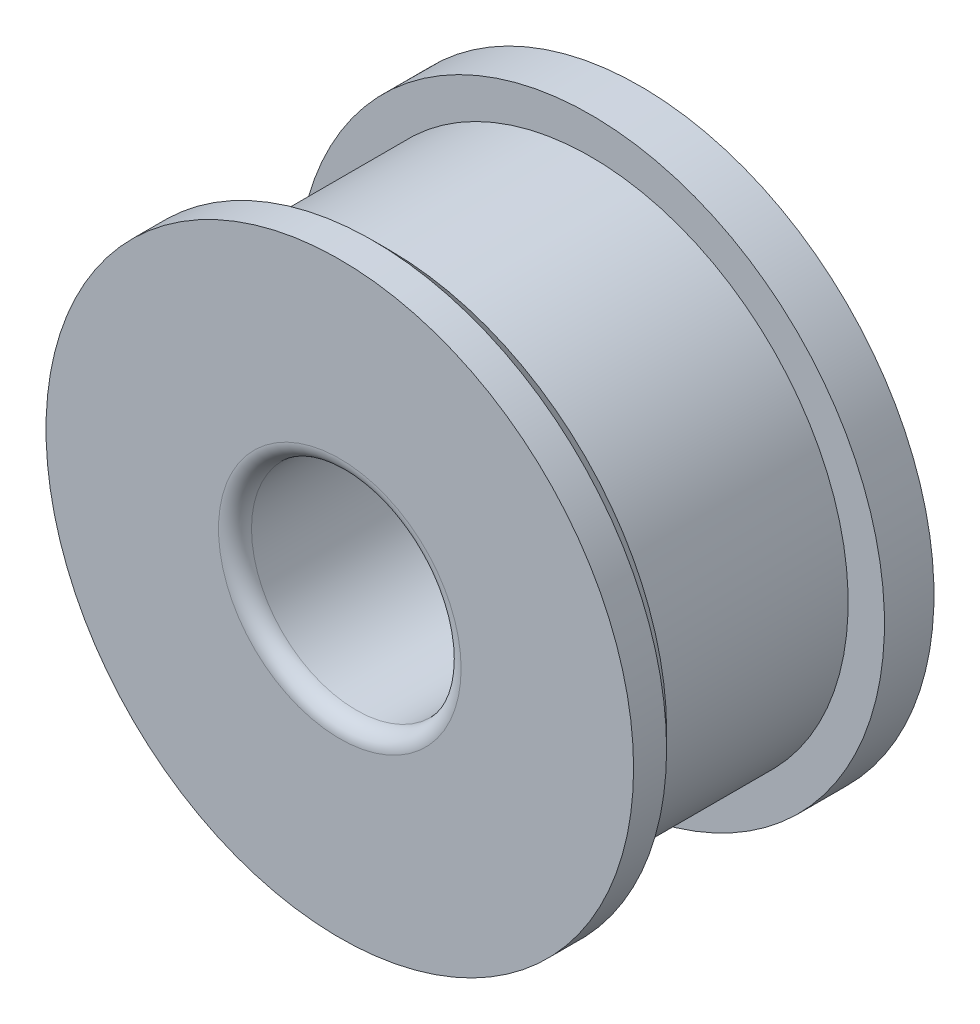
SolidWorks part; units mm, degrees
ref_plane "Plano frontal" through (0, 0, 0) normal (0, 0, 1) x (1, 0, 0)
ref_plane "Plano superior" through (0, 0, 0) normal (0, 1, 0) x (1, 0, 0)
ref_plane "Plano direito" through (0, 0, 0) normal (1, 0, 0) x (0, 0, -1)
sketch "Esboço1" plane through (0, 0, 0) normal (0, 0, 1) x (1, 0, 0)
  line L1 (48.7, 0.625) -> (-48.7, 0.625)
  line L2 (48.7, 0.625) -> (48.7, -0.625)
  line L3 (48.7, -0.625) -> (-48.7, -0.625)
  line L4 (-48.7, 0.625) -> (-48.7, -0.625)
  line L5 (48.7, 0.625) -> (-48.7, -0.625) construction
  line L6 (48.7, -0.625) -> (-48.7, 0.625) construction
  point P0 (0, 0)
  dimension "D1" = 97.4
  dimension "D2" = 1.25
extrude "Ressalto-extrusão1" add sketch "Esboço1" along normal blind 6.2
sketch "Esboço2" plane through (0, -0.625, 0) normal (0, 1, 0) x (1, 0, 0)
  line L0 (48.7, -6.2) -> (48.7, 0) construction
  line L1 (-48.7, 0) -> (48.7, 0)
  line L2 (-48.7, 0) -> (-48.7, -1.25)
  line L3 (-48.7, -1.25) -> (48.7, -1.25)
  line L4 (48.7, 0) -> (48.7, -1.25)
  dimension "D1" = 1.25
extrude "Ressalto-extrusão2" add sketch "Esboço2" along normal blind 40.6 contours L3 L4 L1 L2
fillet "Filete1" radius 1 4 edges at (48.7, 39.975, 0.625) (-48.7, 39.975, 0.625) (48.7, 0, 6.2) (-48.7, 0, 6.2)
sketch "Esboço3" plane through (0, 0, 1.25) normal (0, 0, 1) x (1, 0, 0)
  line L0 (27.7, 34.975) -> (30.7, 34.975) construction
  line L11 (39.7, 33.975) -> (43.7, 33.975)
  line L12 (39.7, 33.975) -> (39.7, 27.975)
  line L13 (39.7, 27.975) -> (43.7, 27.975)
  line L14 (43.7, 33.975) -> (43.7, 27.975)
  line L15 (39.7, 11.975) -> (43.7, 11.975)
  line L16 (39.7, 11.975) -> (39.7, 5.975)
  line L17 (39.7, 5.975) -> (43.7, 5.975)
  line L18 (43.7, 11.975) -> (43.7, 5.975)
  line L19 (-36.7, 12.975) -> (-30.7, 12.975)
  line L20 (-36.7, 12.975) -> (-36.7, 4.975)
  line L21 (-36.7, 4.975) -> (-30.7, 4.975)
  line L22 (-30.7, 12.975) -> (-30.7, 4.975)
  line L23 (27.7, 36.975) -> (30.7, 36.975)
  line L24 (27.7, 32.975) -> (30.7, 32.975)
  line L25 (0, 39.975) -> (0, 2.975) construction
  line L26 (-47.7, 39.975) -> (47.7, 39.975) construction
  line L27 (-47.7, 39.975) -> (47.7, 39.975) construction
  line L28 (-48.7, 38.975) -> (-48.7, 0.625) construction
  line L29 (-36.7, 34.975) -> (-30.7, 34.975)
  line L30 (-36.7, 34.975) -> (-36.7, 26.975)
  line L31 (-36.7, 26.975) -> (-30.7, 26.975)
  line L32 (-30.7, 34.975) -> (-30.7, 26.975)
  line L33 (48.7, 38.975) -> (48.7, 0.625) construction
  line L34 (48.7, 19.8) -> (0, 19.8) construction
  circle A5 centre (-43.7, 4.975) radius 2
  circle A6 centre (0, 4.975) radius 2
  circle A7 centre (38.95, 19.8) radius 2.5
  circle A8 centre (14.7, 19.8) radius 6
  arc A9 (27.7, 36.975) -> (27.7, 32.975) centre (27.7, 34.975) ccw
  arc A10 (30.7, 32.975) -> (30.7, 36.975) centre (30.7, 34.975) ccw
  point P22 (29.2, 34.975)
  point P33 (25.7, 34.975)
  point P34 (32.7, 34.975)
  dimension "D14" = 5
  dimension "D16" = 16
  dimension "D27" = 4
  dimension "D3" = 4
  dimension "D6" = 12
  dimension "D17" = 5
  dimension "D4" = 35
  dimension "D8" = 34
  dimension "D9" = 6
  dimension "D10" = 4
  dimension "D11" = 6
  dimension "D12" = 4
  dimension "D13" = 5
  dimension "D15" = 6
  dimension "D18" = 9.75
  dimension "D19" = 8
  dimension "D20" = 6
  dimension "D21" = 8
  dimension "D22" = 6
  dimension "D23" = 12
  dimension "D24" = 12
  dimension "D25" = 5
  dimension "D26" = 14
  dimension "D28" = 5
  dimension "D29" = 35
  dimension "D30" = 0
  dimension "D31" = 4
  dimension "D32" = 7
  dimension "D33" = 3
  dimension "D34" = 16
extrude "Corte-extrusão1" cut sketch "Esboço3" against normal blind 40.6
sketch "Esboço5" plane through (0, 0, 0) normal (0, 0, -1) x (-1, 0, 0)
  line L0 (-20.7, 19.8) -> (48.7, 19.8) construction
  line L1 (48.7, 38.975) -> (48.7, -0.625) construction
  line L2 (47.7, 39.975) -> (-47.7, 39.975) construction
  line L3 (48.7, 23.975) -> (48.7, 19.8) construction
  circle A0 centre (4.1, 23.975) radius 2
  circle A1 centre (25.7, 19.8) radius 3
  circle A2 centre (-14.7, 19.8) radius 6 construction
  dimension "D1" = 23
  dimension "6" = 6
  dimension "D2" = 4
  dimension "D3" = 16
  dimension "D4" = 44.6
sketch "Esboço6" plane through (0, 0, 0) normal (0, 0, -1) x (-1, 0, 0)
  circle A0 centre (25.7, 19.8) radius 3
  dimension "D1" = 6
extrude "Ressalto-extrusão3" add sketch "Esboço6" against normal blind 22.5
sketch "Esboço7" plane through (0, 0, 0) normal (0, 0, -1) x (-1, 0, 0)
  circle A0 centre (4.1, 23.975) radius 2.25
  dimension "D1" = 4.5
extrude "Ressalto-extrusão4" add sketch "Esboço7" against normal blind 12.3
fillet "Filete2" radius 0.25 2 edges at (-6.35, 23.975, 12.3) (-28.7, 19.8, 22.5)
sketch "Esboço12" plane through (0, 0, 0) normal (0, 0, 1) x (1, 0, 0)
  circle A0 centre (-4.1, 23.975) radius 4
  dimension "D1" = 8
extrude "Ressalto-extrusão7" add sketch "Esboço12" along normal blind 3
sketch "Esboço13" plane through (0, 0, 0) normal (0, 0, -1) x (-1, 0, 0)
  circle A0 centre (25.7, 19.8) radius 4.5
  dimension "D1" = 9
extrude "Ressalto-extrusão8" add sketch "Esboço13" against normal blind 8.1
sketch "Esboço8" plane through (0, 0, 3) normal (0, 0, 1) x (1, 0, 0)
  circle A0 centre (-4.1, 23.975) radius 16.365
  circle A1 centre (-4.1, 23.975) radius 2.3
  dimension "D1" = 32.73
  dimension "D2" = 4.6
extrude "Ressalto-extrusão5" add sketch "Esboço8" along normal blind 4
sketch "Esboço9" plane through (0, 0, 3) normal (0, 0, 1) x (1, 0, 0)
  circle A1 centre (-4.1, 23.975) radius 4
  circle A2 centre (-4.1, 23.975) radius 2.3
  dimension "D1" = 8
extrude "Ressalto-extrusão6" add sketch "Esboço9" along normal blind 8.9
sketch "Esboço10" plane through (0, 0, 7) normal (0, 0, 1) x (1, 0, 0)
  circle A0 centre (-4.1, 23.975) radius 4.9
  circle A1 centre (-4.1, 23.975) radius 13.865
  circle A2 centre (-4.1, 23.975) radius 16.365 construction
  dimension "D1" = 9.8
  dimension "D2" = 2.5
extrude "Corte-extrusão2" cut sketch "Esboço10" against normal blind 1
sketch "Esboço11" plane through (0, 0, 3) normal (0, 0, -1) x (-1, 0, 0)
  circle A1 centre (4.1, 23.975) radius 13.86
  circle A2 centre (4.1, 23.975) radius 4.9
extrude "Corte-extrusão3" cut sketch "Esboço11" against normal blind 1
sketch "Esboço14" plane through (0, 0, 8.1) normal (0, 0, 1) x (1, 0, 0)
  circle A0 centre (-25.7, 19.8) radius 18.34
  circle A1 centre (-25.7, 19.8) radius 3.1
  circle A2 centre (-25.7, 19.8) radius 3 construction
  dimension "D1" = 36.68
  dimension "D2" = 0.1
extrude "Ressalto-extrusão9" add sketch "Esboço14" along normal blind 4
sketch "Esboço15" plane through (0, 0, 8.1) normal (0, 0, 1) x (1, 0, 0)
  circle A0 centre (-25.7, 19.8) radius 7.8
  circle A1 centre (-25.7, 19.8) radius 3.1
  dimension "D1" = 15.6
extrude "Ressalto-extrusão10" add sketch "Esboço15" along normal blind 11.6
sketch "Esboço16" plane through (0, 0, 19.7) normal (0, 0, 1) x (1, 0, 0)
  circle A0 centre (-25.7, 19.8) radius 3.1
  circle A1 centre (-25.7, 19.8) radius 8.9
  dimension "D1" = 17.8
extrude "Ressalto-extrusão11" add sketch "Esboço16" against normal blind 1.5
chamfer "Chanfro1" distance 0.5 angle 45 1 edges at (-16.8, 19.8, 18.2)
sketch "Esboço17" plane through (0, 0, 19.7) normal (0, 0, 1) x (1, 0, 0)
  circle A0 centre (-25.7, 19.8) radius 3.1
  circle A1 centre (-25.7, 19.8) radius 3.5
  dimension "D1" = 7
extrude "Ressalto-extrusão12" add sketch "Esboço17" along normal blind 0.5
sketch "Esboço18" plane through (0, 0, 12.1) normal (0, 0, 1) x (1, 0, 0)
  circle A0 centre (-25.7, 19.8) radius 15.84
  circle A1 centre (-25.7, 19.8) radius 8.9
  circle A2 centre (-25.7, 19.8) radius 18.34 construction
  dimension "D1" = 2.5
  dimension "D2" = 17.8
extrude "Corte-extrusão4" cut sketch "Esboço18" against normal blind 1
sketch "Esboço19" plane through (0, 0, 8.1) normal (0, 0, -1) x (-1, 0, 0)
  circle A0 centre (25.7, 19.8) radius 8.9
  circle A1 centre (25.7, 19.8) radius 15.825
extrude "Corte-extrusão5" cut sketch "Esboço19" against normal blind 1
sketch "Esboço20" plane through (0, 0, 20.2) normal (0, 0, 1) x (1, 0, 0)
  line L0 (-28.3227, 20.6269) -> (-29.675, 21.0533)
  line L3 (-23.7555, 21.7445) -> (-22.4747, 23.0253)
  line L4 (-25.2225, 22.5082) -> (-24.9763, 23.9046)
  line L5 (-23.7555, 17.8555) -> (-22.4747, 16.5747)
  line L6 (-25.2225, 17.0918) -> (-24.9763, 15.6954)
  line L7 (-28.3227, 18.9731) -> (-29.675, 18.5467)
  arc A0 (-22.6425, 24.5746) -> (-22.6425, 15.0254) centre (-25.7, 19.8) ccw
  arc A1 (-25.4411, 24.4906) -> (-29.9802, 21.7362) centre (-25.7, 19.8) ccw
  arc A2 (-28.3227, 20.6269) -> (-28.3227, 18.9731) centre (-25.7, 19.8) ccw
  arc A3 (-23.7555, 21.7445) -> (-25.2225, 22.5082) centre (-25.7, 19.8) ccw
  arc A4 (-25.2225, 17.0918) -> (-23.7555, 17.8555) centre (-25.7, 19.8) ccw
  arc A5 (-29.9802, 17.8638) -> (-25.4411, 15.1094) centre (-25.7, 19.8) ccw
  arc A6 (-22.4747, 16.5747) -> (-22.6425, 15.0254) centre (-23.1818, 15.8675) cw
  arc A7 (-22.4747, 23.0253) -> (-22.6425, 24.5746) centre (-23.1818, 23.7325) ccw
  arc A8 (-25.4411, 15.1094) -> (-24.9763, 15.6954) centre (-25.4687, 15.6086) ccw
  arc A9 (-25.4411, 24.4906) -> (-24.9763, 23.9046) centre (-25.4687, 23.9914) cw
  arc A10 (-29.9802, 17.8638) -> (-29.675, 18.5467) centre (-29.5246, 18.0698) cw
  arc A11 (-29.9802, 21.7362) -> (-29.675, 21.0533) centre (-29.5246, 21.5302) ccw
  dimension "D2" = 1
  dimension "D3" = 0.5
  dimension "D1" = 35
  dimension "D4" = 35
  dimension "D5" = 35
extrude "Ressalto-extrusão13" add sketch "Esboço20" along normal blind 0.5
sketch "Esboço21" plane through (0, 0, 0) normal (0, 0, -1) x (-1, 0, 0)
  line L0 (-29.3939, 34.975) -> (0, 4.975) construction
  line L1 (3.3061, 4.975) -> (-3.6939, 4.975) construction
  line L2 (3.5952, 5.1615) -> (2.7796, 20.8817)
  line L3 (-13.4337, 37.4293) -> (-29.134, 38.5656)
  line L4 (0, 1.375) -> (-4.8727, 1.375)
  line L5 (-32.9939, 34.975) -> (-32.9939, 30.076)
  line L6 (-32.9939, 30.076) -> (-30.4878, 27.5182)
  line L7 (-7.4776, 4.0335) -> (-4.8727, 1.375)
  circle A2 centre (0, 4.975) radius 1.75
  circle A3 centre (-29.3939, 34.975) radius 1.75
  arc A4 (-30.4878, 27.5182) -> (-7.4776, 4.0335) centre (-14.6969, 19.975) ccw
  arc A5 (0, 1.375) -> (3.5952, 5.1615) centre (0, 4.975) ccw
  arc A7 (-29.134, 38.5656) -> (-32.9939, 34.975) centre (-29.3939, 34.975) ccw
  arc A9 (2.7796, 20.8817) -> (-13.4337, 37.4293) centre (-14.6969, 19.975) ccw
  dimension "D2" = 3.5
  dimension "D3" = 3.5
  dimension "D4" = 35
  dimension "D5" = 7.2
  dimension "D1" = 42
  dimension "D7" = 6
extrude "Ressalto-extrusão14" add sketch "Esboço21" along normal blind 0.92
sketch "Esboço23" plane through (0, 0, 0) normal (0, 0, 1) x (1, 0, 0)
  circle A0 centre (14.7, 19.8) radius 17.675
extrude "Ressalto-extrusão15" add sketch "Esboço23" against normal blind 15
fillet "Filete4" radius 1 1 edges at (32.375, 19.8, -15)
sketch "Esboço24" plane through (0, 0, -0.92) normal (0, 0, -1) x (-1, 0, 0)
  circle A0 centre (0, 4.975) radius 1.75
  circle A1 centre (0, 4.975) radius 2.05
  circle A2 centre (-29.3939, 34.975) radius 1.75
  circle A3 centre (-29.3939, 34.975) radius 2.05
  dimension "D1" = 0.3
  dimension "D2" = 0.3
extrude "Ressalto-extrusão16" add sketch "Esboço24" along normal blind 1
sketch "Esboço25" plane through (0, 0, -15) normal (0, 0, -1) x (-1, 0, 0)
  circle A0 centre (-14.7, 19.8) radius 2.5
  dimension "D1" = 5
extrude "Ressalto-extrusão17" add sketch "Esboço25" along normal blind 0.1
sketch "Esboço26" plane through (0, 0, -15.1) normal (0, 0, -1) x (-1, 0, 0)
  circle A0 centre (-14.7, 19.8) radius 1
  dimension "D1" = 2
extrude "Ressalto-extrusão18" add sketch "Esboço26" along normal blind 0.5
fillet "Filete6" radius 0.1 1 edges at (12.2, 19.8, -15.1)
sketch "Esboço27" plane through (0, 0, -15) normal (0, 0, 1) x (1, 0, 0)
  circle A0 centre (14.7, 19.8) radius 4.99
  dimension "D1" = 9.98
extrude "Ressalto-extrusão19" add sketch "Esboço27" along normal blind 16.57
sketch "Esboço28" plane through (0, 0, -15.6) normal (0, 0, -1) x (-1, 0, 0)
  circle A0 centre (-14.7, 19.8) radius 1
extrude "Ressalto-extrusão20" add sketch "Esboço28" against normal blind 25
fillet "Filete5" radius 0.25 2 edges at (13.7, 19.8, -15.6) (13.7, 19.8, 9.4)
ref_plane "Plano2" through (0, 0, 9.15) normal (0, 0, 1) x (1, 0, 0)
sketch "Esboço29" plane through (0, 0, 9.15) normal (0, 0, 1) x (1, 0, 0)
  circle A0 centre (14.7, 19.8) radius 3.59
  dimension "D1" = 7.18
extrude "Ressalto-extrusão21" add sketch "Esboço29" against normal blind 6
sketch "Esboço30" plane through (0, 0, 1.25) normal (0, 0, 1) x (1, 0, 0)
  circle A0 centre (0, 4.975) radius 2.7
  circle A1 centre (29.3939, 34.975) radius 2.7
  dimension "D1" = 5.4
  dimension "D2" = 5.4
extrude "Ressalto-extrusão22" add sketch "Esboço30" along normal blind 2
fillet "Filete7" radius 1.4 2 edges at (2.7, 4.975, 3.25) (32.0939, 34.975, 3.25)
sketch "Esboço31" plane through (0, 0, 3.25) normal (0, 0, 1) x (1, 0, 0)
  line L1 (29.0939, 37.175) -> (29.6939, 37.175)
  line L2 (28.8939, 36.975) -> (28.8939, 35.975)
  line L3 (29.0939, 32.775) -> (29.6939, 32.775)
  line L4 (29.8939, 36.975) -> (29.8939, 35.975)
  line L7 (31.3939, 35.475) -> (30.3939, 35.475)
  line L8 (31.5939, 35.275) -> (31.5939, 34.675)
  line L9 (31.3939, 34.475) -> (30.3939, 34.475)
  line L10 (27.1939, 35.275) -> (27.1939, 34.675)
  line L15 (28.8939, 33.975) -> (28.8939, 32.975)
  line L17 (29.8939, 33.975) -> (29.8939, 32.975)
  line L18 (28.3939, 35.475) -> (27.3939, 35.475)
  line L19 (28.3939, 34.475) -> (27.3939, 34.475)
  line L42 (-0.1421, 7.325) -> (0.4579, 7.325)
  line L43 (-0.3421, 7.125) -> (-0.3421, 6.125)
  line L44 (-0.1421, 2.925) -> (0.4579, 2.925)
  line L45 (0.6579, 7.125) -> (0.6579, 6.125)
  line L46 (2.1579, 5.625) -> (1.1579, 5.625)
  line L47 (2.3579, 5.425) -> (2.3579, 4.825)
  line L48 (2.1579, 4.625) -> (1.1579, 4.625)
  line L49 (-2.0421, 5.425) -> (-2.0421, 4.825)
  line L50 (-0.3421, 4.125) -> (-0.3421, 3.125)
  line L51 (0.6579, 4.125) -> (0.6579, 3.125)
  line L52 (-0.8421, 5.625) -> (-1.8421, 5.625)
  line L53 (-0.8421, 4.625) -> (-1.8421, 4.625)
  arc A0 (29.8939, 33.975) -> (30.3939, 34.475) centre (30.3939, 33.975) cw
  arc A1 (28.8939, 33.975) -> (28.3939, 34.475) centre (28.3939, 33.975) ccw
  arc A2 (29.8939, 35.975) -> (30.3939, 35.475) centre (30.3939, 35.975) ccw
  arc A3 (28.8939, 35.975) -> (28.3939, 35.475) centre (28.3939, 35.975) cw
  arc A4 (28.8939, 32.975) -> (29.0939, 32.775) centre (29.0939, 32.975) ccw
  arc A5 (29.6939, 32.775) -> (29.8939, 32.975) centre (29.6939, 32.975) ccw
  arc A6 (31.5939, 34.675) -> (31.3939, 34.475) centre (31.3939, 34.675) cw
  arc A7 (31.3939, 35.475) -> (31.5939, 35.275) centre (31.3939, 35.275) cw
  arc A8 (29.6939, 37.175) -> (29.8939, 36.975) centre (29.6939, 36.975) cw
  arc A9 (29.0939, 37.175) -> (28.8939, 36.975) centre (29.0939, 36.975) ccw
  arc A10 (27.3939, 35.475) -> (27.1939, 35.275) centre (27.3939, 35.275) ccw
  arc A11 (27.3939, 34.475) -> (27.1939, 34.675) centre (27.3939, 34.675) cw
  circle A24 centre (29.3939, 34.975) radius 1.3 construction
  arc A37 (0.6579, 4.125) -> (1.1579, 4.625) centre (1.1579, 4.125) cw
  arc A38 (-0.3421, 4.125) -> (-0.8421, 4.625) centre (-0.8421, 4.125) ccw
  arc A39 (0.6579, 6.125) -> (1.1579, 5.625) centre (1.1579, 6.125) ccw
  arc A40 (-0.3421, 6.125) -> (-0.8421, 5.625) centre (-0.8421, 6.125) cw
  arc A41 (-0.3421, 3.125) -> (-0.1421, 2.925) centre (-0.1421, 3.125) ccw
  arc A42 (0.4579, 2.925) -> (0.6579, 3.125) centre (0.4579, 3.125) ccw
  arc A43 (2.3579, 4.825) -> (2.1579, 4.625) centre (2.1579, 4.825) cw
  arc A44 (2.1579, 5.625) -> (2.3579, 5.425) centre (2.1579, 5.425) cw
  arc A45 (0.4579, 7.325) -> (0.6579, 7.125) centre (0.4579, 7.125) cw
  arc A46 (-0.1421, 7.325) -> (-0.3421, 7.125) centre (-0.1421, 7.125) ccw
  arc A47 (-1.8421, 5.625) -> (-2.0421, 5.425) centre (-1.8421, 5.425) ccw
  arc A48 (-1.8421, 4.625) -> (-2.0421, 4.825) centre (-1.8421, 4.825) cw
  point P0 (0, 4.975)
  point P6 (29.3939, 34.975)
  point P19 (28.8939, 34.475)
  point P24 (28.8939, 35.475)
  point P27 (28.8939, 32.775)
  point P30 (29.8939, 32.775)
  point P33 (31.5939, 34.475)
  point P36 (31.5939, 35.475)
  point P39 (29.8939, 37.175)
  point P44 (27.1939, 35.475)
  point P128 (0.1579, 5.125)
  point P133 (0.1579, 5.125)
  dimension "D5" = 0.5
  dimension "D6" = 0.2
  dimension "D9" = 0.5
  dimension "D10" = 0.2
  dimension "D1" = 4.4
  dimension "D2" = 4.4
  dimension "D3" = 1
  dimension "D4" = 1
extrude "Corte-extrusão6" cut sketch "Esboço31" against normal blind 1.4
sketch "Esboço32" plane through (0, 0, 1.25) normal (0, 0, -1) x (-1, 0, 0)
  circle A0 centre (0, 4.975) radius 1.75
  circle A1 centre (-29.3939, 34.975) radius 1.75
extrude "Ressalto-extrusão23" add sketch "Esboço32" along normal blind 7.8
chamfer "Chanfro2" distance 1 angle 25 2 edges at (-1.75, 4.975, -6.55) (27.6439, 34.975, -6.55) first distance on face at (-1.75, 4.975, -1.92) first distance on face at (27.6439, 34.975, -1.92)
sketch "Esboço33" plane through (0, 0, -0.92) normal (0, 0, -1) x (-1, 0, 0)
  line L1 (3.2243, 12.8461) -> (4.2922, 22.7889)
  line L2 (4.2922, 22.7889) -> (2.6901, 22.961)
  line L3 (3.2243, 12.8461) -> (1.6222, 13.0182)
  arc A4 (1.6222, 13.0182) -> (2.6901, 22.961) centre (-14.7, 19.8) ccw
  arc A7 (1.6222, 13.0182) -> (2.6901, 22.961) centre (-14.7, 19.8) ccw
  arc M4 (2.9127, 18.3164) -> (-7.2301, 3.781) centre (-14.7, 19.8) cw
  line M8 (3.5952, 5.1615) -> (2.9127, 18.3164)
  dimension "D1" = 10
  dimension "D2" = 90
extrude "Ressalto-extrusão24" add sketch "Esboço33" along normal blind 10 contours A4 L3 L1 L2 M8 | L3 M8 M4 region at (-3.4256, 19.3944, -0.92) region at (-2.6269, 14.5261, -0.92)
sketch "Esboço34" plane through (-1.8235, -0.1959, 0) normal (-0.9943, -0.1068, 0) x (0, 0, 1)
  line L0 (-5.92, 23.117) -> (-5.92, 13.117) construction
  line L1 (-10.92, 23.117) -> (-0.92, 23.117) construction
  line L2 (-10.92, 13.117) -> (-0.92, 13.117) construction
  circle A0 centre (-5.92, 18.117) radius 2
  dimension "D1" = 4
extrude "Ressalto-extrusão25" add sketch "Esboço34" along normal blind 5
sketch "Esboço35" plane through (0, 0, 12.1) normal (0, 0, 1) x (1, 0, 0)
  line L0 (-48.7, 38.975) -> (-48.7, 0.625) construction
  circle A0 centre (-398.7, 19.8) radius 7.8
  point P2 (-25.7, 19.8)
  dimension "D1" = 15.6
  dimension "D2" = 350
  dimension "D3" = 0
extrude "Ressalto-extrusão26" add sketch "Esboço35" along normal blind 7.6 separate body
sketch "Esboço37" plane through (0, 0, 19.7) normal (0, 0, 1) x (1, 0, 0)
  circle A0 centre (-398.7, 19.8) radius 8.9
  dimension "D1" = 17.8
extrude "Ressalto-extrusão27" add sketch "Esboço37" against normal blind 1.5
chamfer "Chanfro3" distance 0.5 angle 45 1 edges at (-389.8, 19.8, 18.2)
sketch "Esboço38" plane through (0, 0, 12.1) normal (0, 0, -1) x (-1, 0, 0)
  circle A0 centre (398.7, 19.8) radius 8.9
extrude "Ressalto-extrusão28" add sketch "Esboço38" along normal blind 1.5
sketch "Esboço39" plane through (0, 0, 19.7) normal (0, 0, 1) x (1, 0, 0)
  circle A0 centre (-398.7, 19.8) radius 3.175
  dimension "D1" = 6.35
extrude "Corte-extrusão7" cut sketch "Esboço39" against normal blind 35.5 and the other way blind 16
ref_plane "Plano3" through (0, 0, 13.1) normal (0, 0, 1) x (1, 0, 0)
fillet "Filete11" radius 0.5 1 edges at (0, -0.625, 0)
fillet "Filete12" radius 0.25 1 edges at (0, 0.625, 1.25)
delete or keep bodies "Corpo-Excluir/Manter 1" type delete bodies bodies 131
fillet "Filete13" radius 0.5 2 edges at (-401.875, 19.8, 10.6) (-395.525, 19.8, 19.7)
